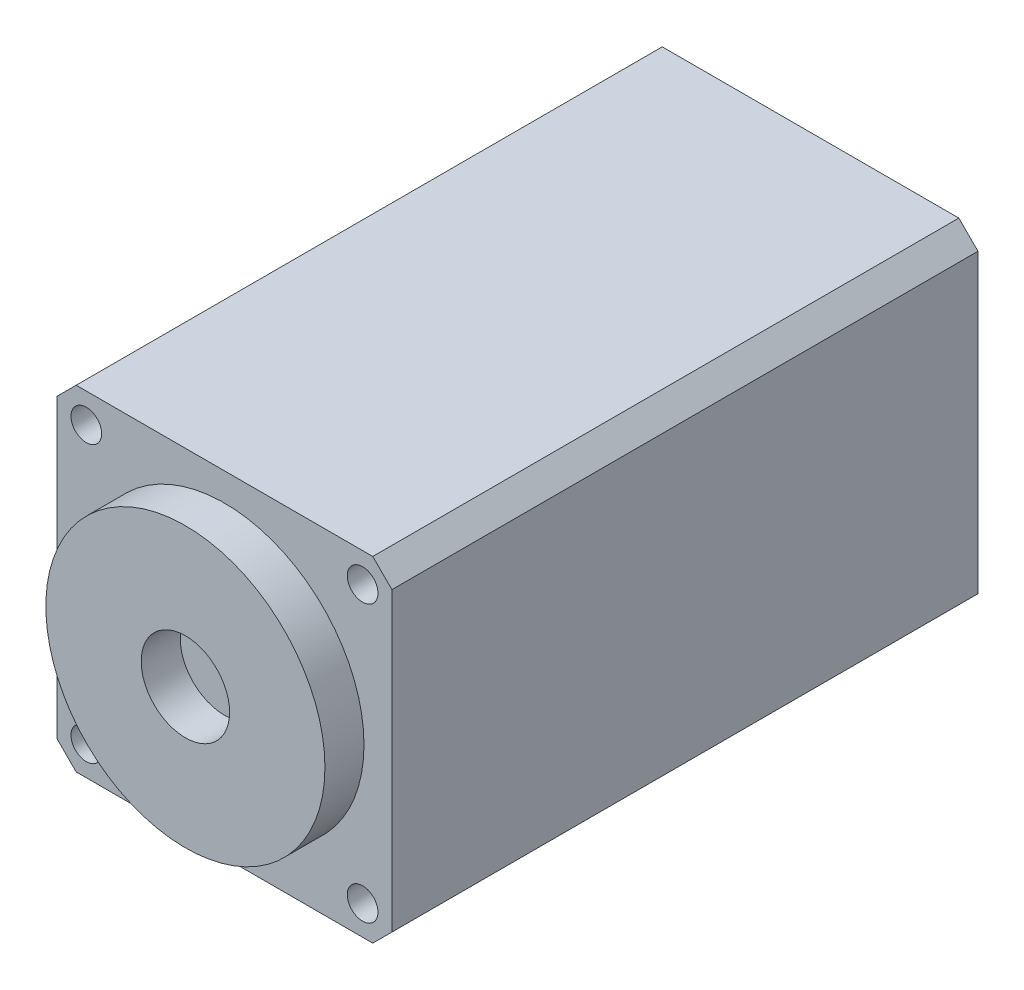
SolidWorks part; units mm, degrees
material "1060 Alloy"
ref_plane "Front Plane" through (0, 0, 0) normal (0, 0, 1) x (1, 0, 0)
ref_plane "Top Plane" through (0, 0, 0) normal (0, 1, 0) x (1, 0, 0)
ref_plane "Right Plane" through (0, 0, 0) normal (1, 0, 0) x (0, 0, -1)
sketch "Sketch1" plane through (0, 0, 0) normal (0, 0, 1) x (1, 0, 0)
  line L0 (-30, -26.5685) -> (-26.5685, -30)
  line L1 (-26.5685, -30) -> (26.5685, -30)
  line L2 (-30, -26.5685) -> (-30, 26.5685)
  line L3 (-26.5685, 30) -> (26.5685, 30)
  line L4 (30, -26.5685) -> (30, 26.5685)
  line L5 (-28.2843, -28.2843) -> (28.2843, 28.2843) construction
  line L6 (-28.2843, 28.2843) -> (30, -30) construction
  line L7 (-26.5685, -30) -> (26.5685, -30)
  line L8 (26.5685, -30) -> (30, -26.5685)
  line L9 (26.5685, 30) -> (30, 26.5685)
  line L10 (-26.5685, 30) -> (-30, 26.5685)
  line L11 (0, 30) -> (0, -30) construction
  line L13 (30, 0) -> (-30, 0) construction
  circle A3 centre (0, 0) radius 35 construction
  circle A6 centre (-24.7487, 24.7487) radius 2.75
  circle A7 centre (24.7487, 24.7487) radius 2.75
  circle A8 centre (-24.7487, -24.7487) radius 2.75
  circle A9 centre (24.7487, -24.7487) radius 2.75
  point P0 (0, 0)
  dimension "D2" = 45
  dimension "D5" = 5.5
  dimension "D1" = 70
  dimension "D3" = 80
  dimension "D4" = 53.1371
  dimension "D6" = 53.1371
  dimension "D7" = 53.1371
  dimension "D8" = 5
extrude "Boss-Extrude1" add sketch "Sketch1" along normal blind 105 contours L3 L10 L2 L0 L1 L8 L4 L9 A9 A8 A7 A6 region at (0, 0, 0)
sketch "Sketch2" plane through (0, 0, 105) normal (0, 0, 1) x (1, 0, 0)
  circle A0 centre (0, 0) radius 25
  circle A1 centre (0, 0) radius 7.9202
  dimension "D1" = 50
extrude "Boss-Extrude2" add sketch "Sketch2" along normal blind 7
sketch "Sketch3" plane through (0, 0, 0) normal (0, 0, -1) x (-1, 0, 0)
  circle A0 centre (0, 0) radius 25
  circle A1 centre (0, 0) radius 7
  dimension "D1" = 50
  dimension "D2" = 14
extrude "Cut-Extrude1" cut sketch "Sketch3" against normal blind 6
extrude "Cut-Extrude2" cut sketch "Sketch3<2>" against normal blind 34 contours A1 region at (0, 0, 0)
sketch "Sketch3<2>" plane through (0, 0, 0) normal (0, 0, -1) x (-1, 0, 0) same geometry as "Sketch3"
